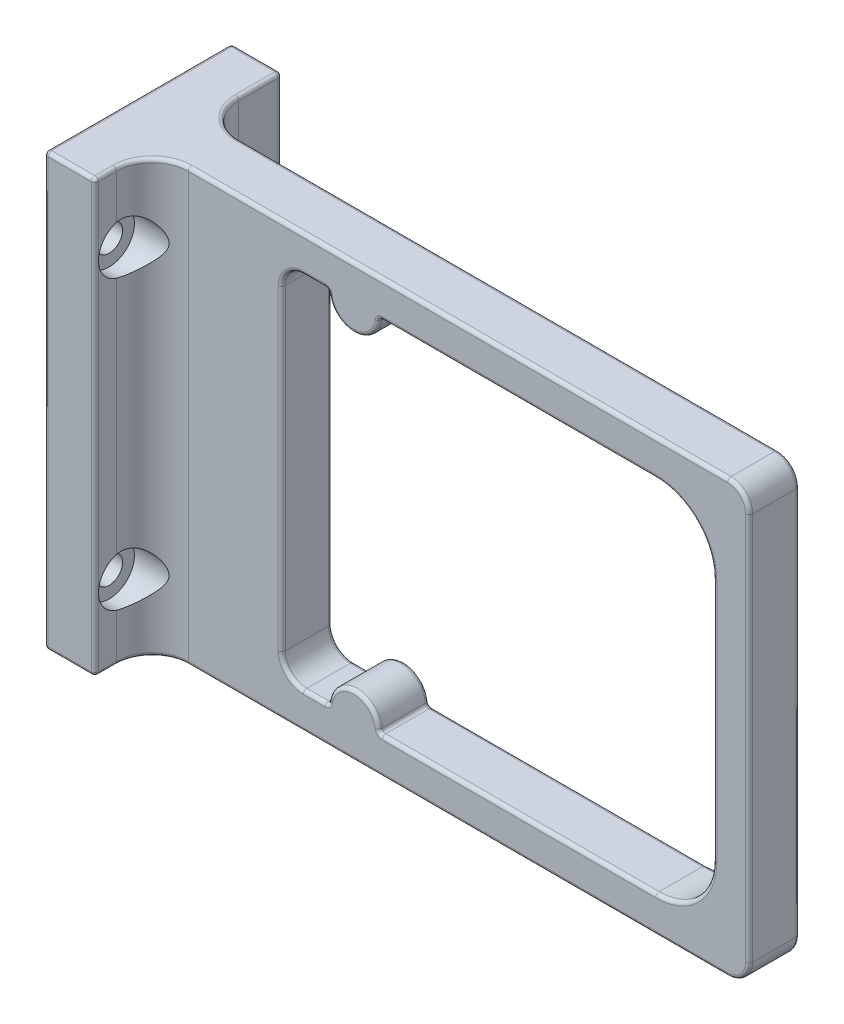
SolidWorks part; units mm, degrees
ref_plane "Front Plane" through (0, 0, 0) normal (0, 0, 1) x (1, 0, 0)
ref_plane "Top Plane" through (0, 0, 0) normal (0, 1, 0) x (1, 0, 0)
ref_plane "Right Plane" through (0, 0, 0) normal (1, 0, 0) x (0, 0, -1)
sketch "Sketch1" plane through (0, 0, 0) normal (0, 0, 1) x (1, 0, 0)
  line L9 (-141, -31) -> (-54, -31)
  line L11 (-54, 29) -> (-141, 29)
  line L12 (-113, 24) -> (-109.5, 24)
  line L13 (-141, 29) -> (-141, -31)
  line L14 (-113, -26) -> (-109.5, -26)
  line L15 (-51, 26) -> (-51, -28)
  line L16 (-56, 16) -> (-56, -18)
  line L17 (-116, 21) -> (-116, -23)
  line L18 (-102.5, 24) -> (-64, 24)
  line L19 (-102.5, -26) -> (-64, -26)
  arc A4 (-54, -31) -> (-51, -28) centre (-54, -28) ccw
  arc A5 (-54, 29) -> (-51, 26) centre (-54, 26) cw
  arc A6 (-64, -26) -> (-56, -18) centre (-64, -18) ccw
  arc A7 (-56, 16) -> (-64, 24) centre (-64, 16) ccw
  arc A13 (-109.5, 24) -> (-102.5, 24) centre (-106, 24) ccw
  arc A15 (-102.5, -26) -> (-109.5, -26) centre (-106, -26) ccw
  arc A16 (-116, -23) -> (-113, -26) centre (-113, -23) ccw
  arc A17 (-116, 21) -> (-113, 24) centre (-113, 21) cw
  dimension "D1" = 3
  dimension "D4" = 8
  dimension "D6" = 7
  dimension "D7" = 3.5
  dimension "D5" = 3
  dimension "D8" = 60
  dimension "D11" = 5
  dimension "D12" = 10
  dimension "D2" = 5
  dimension "D3" = 60
  dimension "D9" = 50
  dimension "D10" = 90
  dimension "D13" = 10
extrude "Boss-Extrude1" add sketch "Sketch1" along normal blind 7
sketch "Sketch2" plane through (0, 0, 7) normal (0, 0, 1) x (1, 0, 0)
  line L0 (-141, 29) -> (-141, -31) construction
  line L1 (-141, 29) -> (-134, 29)
  line L2 (-141, 29) -> (-141, -31)
  line L3 (-141, -31) -> (-134, -31)
  line L4 (-134, 29) -> (-134, -31)
  line L5 (-54, 29) -> (-141, 29) construction
  line L6 (-141, -31) -> (-54, -31) construction
  dimension "D1" = 7
extrude "Boss-Extrude2" add sketch "Sketch2" along normal blind 8 and the other way blind 18
fillet "Fillet1" radius 5 2 edges at (-134, -1, 7) (-134, -1, 0)
sketch "Sketch3" plane through (-134, 0, 0) normal (1, 0, 0) x (0, 0, -1)
  line L2 (-12, -31) -> (-7, -31) construction
  line L3 (-15, -31) -> (-15, 29) construction
  line L4 (-7, 29) -> (-12, 29) construction
  circle A2 centre (-11, 19) radius 1.85
  circle A3 centre (-11, -21) radius 1.85
  point P0 (0, 0)
  dimension "D1" = 10
  dimension "D2" = 10
  dimension "D6" = 3.7
  dimension "D7" = 4
  dimension "D8" = 3.7
extrude "Cut-Extrude1" cut sketch "Sketch3" against normal blind 10 and the other way blind 10
sketch "Sketch4" plane through (-134, 0, 0) normal (1, 0, 0) x (0, 0, -1)
  circle A0 centre (-11, -21) radius 3.5
  circle A2 centre (-11, 19) radius 3.5
  dimension "D1" = 7
  dimension "D3" = 7
extrude "Cut-Extrude2" cut sketch "Sketch4" along normal blind 10 and the other way blind 2
fillet "Fillet2" radius 0.5 28 edges at (-51.8787, -30.1213, 7) (-51.8787, -30.1213, 0) (-51.8787, 28.1213, 7) (-51.8787, 28.1213, 0) (-91.5, 29, 7) (-132.5355, 29, 8.4645) (-134, 29, 13.5) (-141, 29, 2) (-134, 29, -8) (-132.5355, 29, -1.4645) (-91.5, 29, 0) (-51, -1, 7) (-51, -1, 0) (-91.5, -31, 0) (-132.5355, -31, -1.4645) (-134, -31, -8) (-141, -31, 2) (-134, -31, 13.5) (-132.5355, -31, 8.4645) (-91.5, -31, 7) (-137.5, -31, -11) (-134, -1, -11) (-137.5, 29, -11) (-141, -1, -11) (-137.5, 29, 15) (-134, -1, 15) (-137.5, -31, 15) (-141, -1, 15)
fillet "Fillet3" radius 0.5 28 edges at (-83.25, -26, 7) (-58.3431, -23.6569, 7) (-56, -1, 7) (-58.3431, 21.6569, 7) (-83.25, -26, 0) (-58.3431, -23.6569, 0) (-56, -1, 0) (-58.3431, 21.6569, 0) (-111.25, 24, 7) (-115.1213, 23.1213, 7) (-111.25, -26, 7) (-115.1213, -25.1213, 7) (-111.25, 24, 0) (-115.1213, 23.1213, 0) (-111.25, -26, 0) (-115.1213, -25.1213, 0) (-109.5, 24, 3.5) (-106, 20.5, 7) (-106, 20.5, 0) (-102.5, -26, 3.5) (-106, -22.5, 7) (-109.5, -26, 3.5) (-106, -22.5, 0) (-102.5, 24, 3.5) (-83.25, 24, 7) (-83.25, 24, 0) (-116, -1, 7) (-116, -1, 0)
sketch "Sketch5" plane through (0, 0, 0) normal (0, 0, -1) x (-1, 0, 0)
  arc A0 (103.0235, 23.625) -> (108.9765, 23.625) centre (106, 24) ccw construction
  circle A2 centre (106, -26) radius 1.75
  circle A4 centre (56, -26) radius 1.75
  circle A6 centre (56, 24) radius 1.75
  circle A8 centre (106, 24) radius 1.75
  point P0 (105.8052, 24.25)
  dimension "D1" = 3.5
  dimension "D2" = 3.5
  dimension "D3" = 3.5
  dimension "D4" = 3.5
  dimension "D5" = 50
  dimension "D6" = 50
extrude "Cut-Extrude3" cut sketch "Sketch5" against normal blind 5
